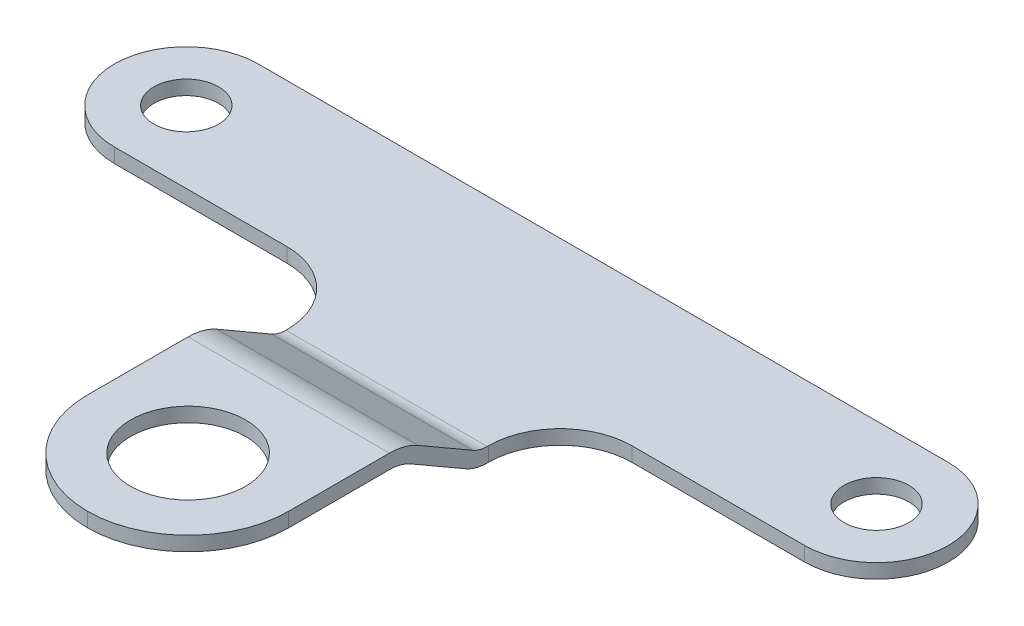
SolidWorks part; units mm, degrees
material "Plain Carbon Steel"
ref_plane "Front Plane" through (0, 0, 0) normal (0, 0, 1) x (1, 0, 0)
ref_plane "Top Plane" through (0, 0, 0) normal (0, 1, 0) x (1, 0, 0)
ref_plane "Right Plane" through (0, 0, 0) normal (1, 0, 0) x (0, 0, -1)
sketch "Sketch1" plane through (0, 0, 0) normal (1, 0, 0) x (0, 0, -1)
  line L0 (0, 0) -> (-15.0709, 0)
  line L1 (-20.3748, 2.5981) -> (-16.5709, 0.4019)
  line L2 (-21.8748, 3) -> (-35.8748, 3)
  arc A0 (-21.8748, 3) -> (-20.3748, 2.5981) centre (-21.8748, 0) cw
  arc A1 (-15.0709, 0) -> (-16.5709, 0.4019) centre (-15.0709, 3) cw
  dimension "D4" = 14
  dimension "D3" = 3
  dimension "D1" = 36
  dimension "D2" = 3
  dimension "D5" = 30
extrude "Extrude-Thin1" add sketch "Sketch1" along normal mid plane 14 thin thin type one direction wall 1
fillet "Fillet1" radius 7 2 edges at (-7, 3.5, 35.8748) (7, 3.5, 35.8748)
sketch "Sketch2" plane through (0, 1, 0) normal (0, 1, 0) x (1, 0, 0)
  circle A2 centre (0, -28.8748) radius 4
  dimension "D4" = 8
extrude "Cut-Extrude1" cut sketch "Sketch2" against normal blind 10 and the other way blind 10
sketch "Sketch3" plane through (0, 0, 0) normal (0, -1, 0) x (1, 0, 0)
  line L0 (24, 5) -> (-24, 5) construction
  line L1 (24, 0) -> (-24, 0)
  line L2 (24, 10) -> (-24, 10)
  line L3 (7, 0) -> (-7, 0) construction
  line L4 (0, 0) -> (0, 5) construction
  arc A0 (24, 0) -> (24, 10) centre (24, 5) ccw
  arc A1 (-24, 10) -> (-24, 0) centre (-24, 5) ccw
  circle A2 centre (24, 5) radius 2.25
  circle A3 centre (-24, 5) radius 2.25
  point P2 (0, 5)
  dimension "D1" = 4.5
  dimension "D2" = 5
  dimension "D3" = 48
extrude "Boss-Extrude1" add sketch "Sketch3" against normal blind 1
fillet "Fillet2" radius 5 2 edges at (7, 0.5, 10) (-7, 0.5, 10)
